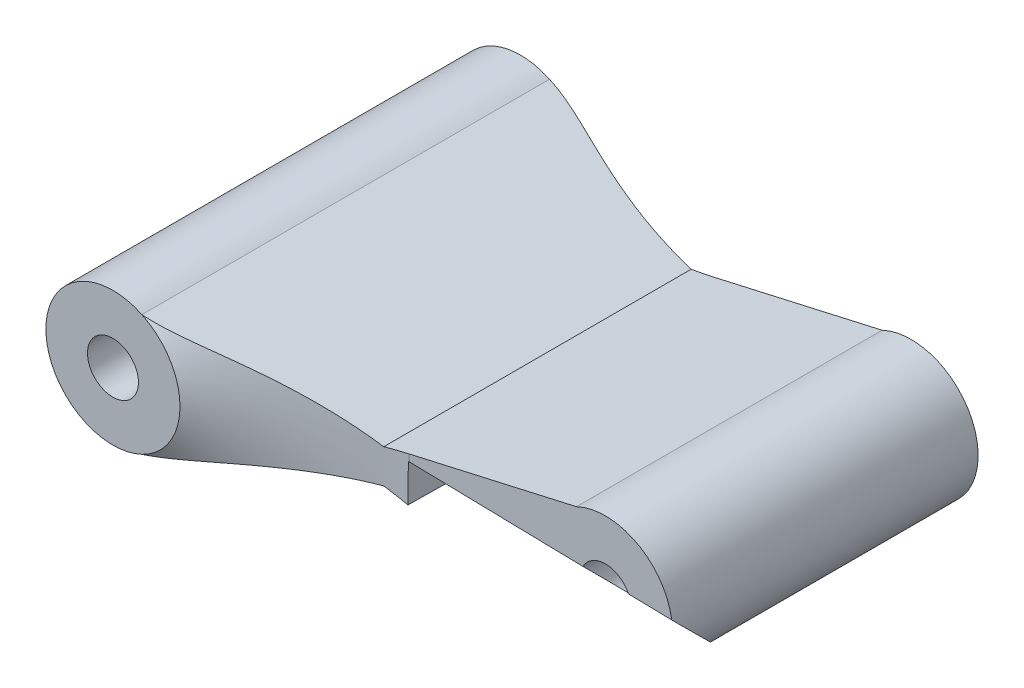
SolidWorks part; units mm, degrees
ref_plane "Front Plane" through (0, 0, 0) normal (0, 0, 1) x (1, 0, 0)
ref_plane "Top Plane" through (0, 0, 0) normal (0, 1, 0) x (1, 0, 0)
ref_plane "Right Plane" through (0, 0, 0) normal (1, 0, 0) x (0, 0, -1)
sketch "Sketch1" plane through (0, 0, 0) normal (0, 0, 1) x (1, 0, 0)
  line L0 (0, 2.475) -> (6.5, 1)
  line L1 (0, 1) -> (13, 1)
  line L2 (0, 1) -> (0, 0)
  line L3 (0, 0) -> (13, 0)
  line L4 (13, 1) -> (13, 0)
  line L5 (6.5, 1) -> (13, 2.475)
  line L6 (13, -1.475) -> (6.5, 0)
  line L7 (0, -1.475) -> (6.5, 0)
  circle A0 centre (0, 0.5) radius 1.975
  circle A1 centre (13, 0.5) radius 1.975
  circle A2 centre (0, 0.5) radius 0.75
  circle A3 centre (13, 0.5) radius 0.75
  dimension "D3" = 3.95
  dimension "D4" = 1.5
  dimension "D1" = 1
  dimension "D2" = 13
extrude "Boss-Extrude1" add sketch "Sketch1" along normal blind 9 contours L1 A0 L0 L7 L3 L2 | L3 A0 L1 L2 | A1 L1 A0 L3 | A0 L1 L0 | A1 L5 L1 | L5 A1 L1 L4 L3 L6 | L1 A1 L3 L4 | A1 L3 L6 | A0 L7 L3 | L5 A1 | L6 A1 | L7 A0 | L0 A0 region at (0.4306, 2.3974, 0) region at (0.414, 2.3242, 0) region at (3.2114, 1.4077, 0) region at (0.4306, -1.3974, 0) region at (6.5, 0.5, 0) region at (9.7886, 1.4077, 0) region at (1.3208, 0.5, 0) region at (3.2114, -0.4077, 0) region at (11.5198, 1.7222, 0) region at (11.6792, 0.5, 0) region at (12.5694, 2.3974, 0) region at (9.7886, -0.4077, 0) region at (12.5694, -1.3974, 0)
sketch "Sketch2" plane through (0, 0, 9) normal (0, 0, 1) x (1, 0, 0)
  circle A0 centre (0, 0.5) radius 0.75
  circle A1 centre (0, 0.5) radius 1.975
  circle A2 centre (0, 0.5) radius 0.75 construction
  arc A3 (0.8525, 2.2816) -> (0.8525, -1.2816) centre (0, 0.5) ccw construction
extrude "Boss-Extrude2" add sketch "Sketch2" along normal blind 1.5 and the other way blind 10.5
fillet "Fillet1" radius 10 1 edges at (1.975, 0.5, 9)
fillet "Fillet2" radius 10 1 edges at (1.975, 0.5, 0)
ref_plane "Plane1" through (-0.086, -3.9382, 3.9392) normal (-0.0154, -0.7069, 0.7071) x (0.9999, -0.0109, 0.0109)
sketch "Sketch5" plane through (-0.086, -3.9382, 3.9392) normal (-0.0154, -0.7069, 0.7071) x (0.9999, -0.0109, 0.0109)
  line L1 (7.2848, 0) -> (20.5415, 0)
  line L2 (7.2848, 0) -> (7.2848, 13.4252)
  line L3 (7.2848, 13.4252) -> (20.5415, 13.4252)
  line L4 (20.5415, 0) -> (20.5415, 13.4252)
extrude "Cut-Extrude1" cut sketch "Sketch5" along normal blind 7
